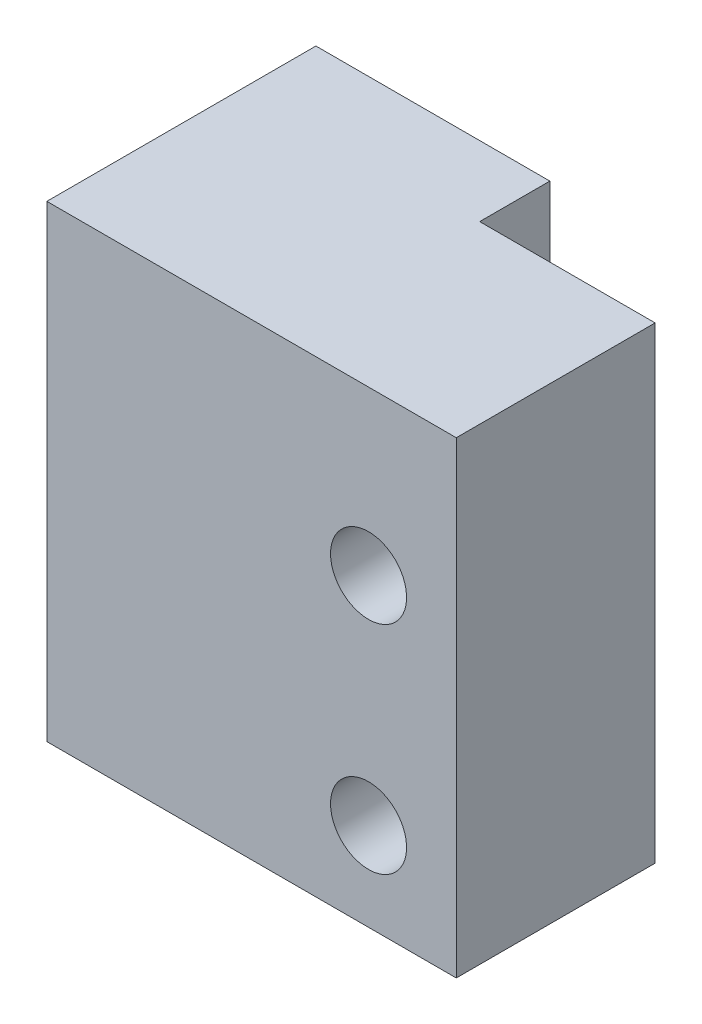
SolidWorks part; units mm, degrees
ref_plane "Front Plane" through (0, 0, 0) normal (0, 0, 1) x (1, 0, 0)
ref_plane "Top Plane" through (0, 0, 0) normal (0, 1, 0) x (1, 0, 0)
ref_plane "Right Plane" through (0, 0, 0) normal (1, 0, 0) x (0, 0, -1)
sketch "Sketch1" plane through (0, 0, 0) normal (0, 1, 0) x (1, 0, 0)
  line L5 (-10, -5.2575) -> (-10, 0.7425)
  line L6 (-10, 0.7425) -> (10, 0.7425)
  line L9 (25, -5.2575) -> (25, -22.2575)
  line L10 (0, -22.2575) -> (0, 0.7425) construction
  line L11 (-10, -5.2575) -> (-10, -22.2575)
  line L12 (10, 0.7425) -> (10, -5.2575)
  line L13 (10, -5.2575) -> (25, -5.2575)
  line L14 (-10, -22.2575) -> (25, -22.2575)
  point P2 (0, 0)
  dimension "D5" = 17
  dimension "D6" = 15
extrude "Boss-Extrude2" add sketch "Sketch1" along normal blind 40
sketch "Sketch3" plane through (0, 0, 0) normal (0, -1, 0) x (1, 0, 0)
  line L0 (0, -0.7425) -> (0, 22.2575) construction
  line L1 (10, -0.7425) -> (-10, -0.7425) construction
  circle A0 centre (0, 9.2575) radius 4
  dimension "D1" = 8
  dimension "D2" = 10
extrude "Cut-Extrude1" cut sketch "Sketch3" against normal blind 35
sketch "Sketch4" plane through (0, 0, 5.2575) normal (0, 0, -1) x (-1, 0, 0)
  line L0 (-25, 20) -> (-10, 20) construction
  line L1 (-25, 40) -> (-25, 0) construction
  line L2 (-10, 40) -> (-10, 0) construction
  line L3 (-17.5, 40) -> (-17.5, 0) construction
  line L4 (-25, 40) -> (-10, 40) construction
  line L5 (-25, 0) -> (-10, 0) construction
  circle A0 centre (-17.5, 26.0458) radius 3.25
  circle A2 centre (-17.5, 7.5353) radius 3.25
  dimension "D1" = 6.5
  dimension "D2" = 6.5
extrude "Cut-Extrude2" cut sketch "Sketch4" against normal up to next
sketch "Sketch5" plane through (0, 0, 0) normal (0, -1, 0) x (1, 0, 0)
  line L0 (0, -0.7425) -> (0, 22.2575) construction
  line L1 (10, -0.7425) -> (-10, -0.7425) construction
  line L2 (-10, 22.2575) -> (25, 22.2575) construction
